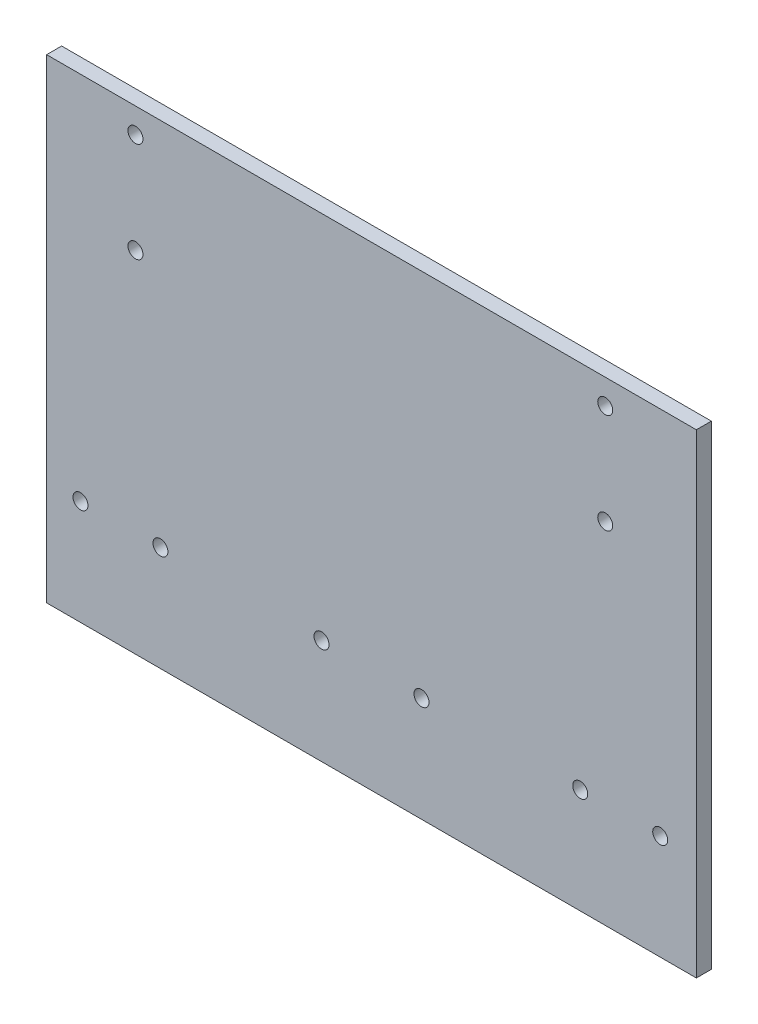
SolidWorks part; units mm, degrees
ref_plane "前视基准面" through (0, 0, 0) normal (0, 0, 1) x (1, 0, 0)
ref_plane "上视基准面" through (0, 0, 0) normal (0, 1, 0) x (1, 0, 0)
ref_plane "右视基准面" through (0, 0, 0) normal (1, 0, 0) x (0, 0, -1)
sketch "草图1" plane through (0, 0, 0) normal (0, 0, 1) x (1, 0, 0)
  line L1 (65, -47.5) -> (-65, -47.5)
  line L2 (65, -47.5) -> (65, 47.5)
  line L3 (65, 47.5) -> (-65, 47.5)
  line L4 (-65, -47.5) -> (-65, 47.5)
  line L5 (65, -47.5) -> (-65, 47.5) construction
  line L6 (65, 47.5) -> (-65, -47.5) construction
  point P0 (0, 0)
  dimension "D1" = 130
  dimension "D2" = 95
extrude "凸台-拉伸1" add sketch "草图1" along normal blind 3
sketch "草图2" plane through (0, 0, 3) normal (0, 0, 1) x (1, 0, 0)
  line L0 (0, -47.5) -> (0, -26.5) construction
  line L1 (-65, -47.5) -> (65, -47.5) construction
  line L2 (0, -26.5) -> (10, -26.5) construction
  circle A0 centre (10, -26.5) radius 1.5
  circle A1 centre (-10, -26.5) radius 1.5
  dimension "D3" = 3
  dimension "D1" = 21
  dimension "D2" = 10
extrude "切除-拉伸1" cut sketch "草图2" against normal blind 10
sketch "草图3" plane through (0, 0, 0) normal (0, 0, -1) x (-1, 0, 0)
  circle A0 centre (-57.7671, -26.5) radius 1.5
  circle A1 centre (-41.7671, -26.5) radius 1.5
  circle A2 centre (42.2329, -26.5) radius 1.5
  circle A4 centre (58.2329, -26.5) radius 1.5
extrude "切除-拉伸2" cut sketch "草图3" against normal blind 10
sketch "草图4" plane through (0, 0, 0) normal (0, 0, -1) x (-1, 0, 0)
  circle A0 centre (-46.7671, 42.5) radius 1.5
  circle A1 centre (-46.7671, 22.5) radius 1.5
  circle A2 centre (47.2329, 42.5) radius 1.5
  circle A3 centre (47.2329, 22.5) radius 1.5
extrude "切除-拉伸3" cut sketch "草图4" against normal blind 10
